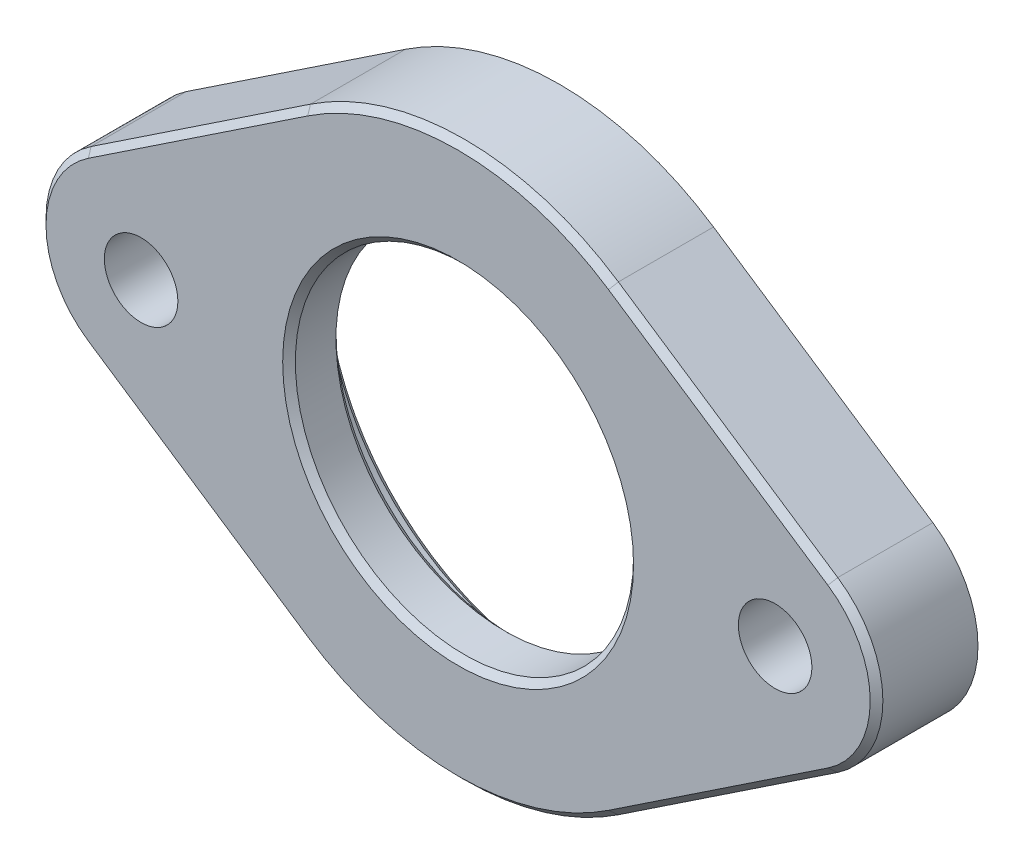
SolidWorks part; units mm, degrees
material "ABS"
ref_plane "Front Plane" through (0, 0, 0) normal (0, 0, 1) x (1, 0, 0)
ref_plane "Top Plane" through (0, 0, 0) normal (0, 1, 0) x (1, 0, 0)
ref_plane "Right Plane" through (0, 0, 0) normal (1, 0, 0) x (0, 0, -1)
sketch "Sketch1" plane through (0, 0, 0) normal (0, 0, 1) x (1, 0, 0)
  line L0 (-12.5, 0) -> (12.5, 0)
  line L1 (-6.0703, -9.0984) -> (-14.72, -3.3274)
  line L2 (-6.0703, 9.0984) -> (-14.72, 3.3274)
  line L3 (6.0703, 9.0984) -> (14.72, 3.3274)
  line L4 (6.0703, -9.0984) -> (14.72, -3.3274)
  circle A0 centre (0, 0) radius 6.6675
  circle A1 centre (0, 0) radius 8.9375
  circle A2 centre (0, 0) radius 10.9375
  circle A3 centre (-12.5, 0) radius 4
  circle A4 centre (12.5, 0) radius 4
  point P7 (0, 0)
  dimension "D1" = 13.335
  dimension "D2" = 17.875
  dimension "D4" = 8
  dimension "D3" = 2
  dimension "D5" = 25
extrude "Boss-Extrude1" add sketch "Sketch1" along normal blind 4 contours A3 L0 A2 L2 | A3 L1 A2 L0 | A3 | A4 L3 A2 L0 | A4 | A4 L0 A2 L4 | A2 region at (13.2988, 0, 0) region at (10.617, 5.2562, 0) region at (10.617, -5.2562, 0) region at (-10.617, 5.2562, 0) region at (-13.2988, 0, 0) region at (-10.617, -5.2562, 0)
extrude "Cut-Extrude1" cut sketch "Sketch1<4>" against normal through all both and the other way through all contours L0 A0 | L0 A0 region at (0, -2.8298, 0) region at (0, 2.8298, 0)
sketch "Sketch1<4>" plane through (0, 0, 0) normal (0, 0, 1) x (1, 0, 0) same geometry as "Sketch1"
extrude "Cut-Extrude2" cut sketch "Sketch1<6>" along normal blind 1.9 and the other way through all contours A1
sketch "Sketch1<6>" plane through (0, 0, 0) normal (0, 0, 1) x (1, 0, 0) same geometry as "Sketch1"
sketch "Sketch2" plane through (0, 0, 4) normal (0, 0, 1) x (1, 0, 0)
  point P0 (-12.5, 0)
  point P3 (12.5, 0)
hole_wizard "M2.5 Clearance Hole1" positions "Sketch2" profile "Sketch3" hole size "M2.5" standard "ANSI Metric" end condition through all
sketch "Sketch3" plane through (-12.5, 0, 4) normal (1, 0, 0) x (0, -1, 0)
  line L0 (0, 0) -> (0, 4)
  line L1 (0, 4) -> (1.45, 4)
  line L2 (1.45, 4) -> (1.45, 0)
  line L5 (1.45, 0) -> (0, 0)
  line L11 (0, -6.35) -> (0, 107.95) construction
  dimension "Thru Hole Dia." = 2.9
  dimension "Thru Hole Depth" = 4
chamfer "Chamfer1" distance 0.25 angle 45 12 edges at (6.6675, 0, 4) (6.6675, 0, 1.9) (8.9375, 0, 0) (8.9375, 0, 1.9) (10.3952, -6.2129, 4) (16.5, 0, 4) (0, -10.9375, 4) (10.3952, 6.2129, 4) (-10.3952, -6.2129, 4) (0, 10.9375, 4) (-16.5, 0, 4) (-10.3952, 6.2129, 4)
equation "\"D2@Sketch1\"=15.875mm+2"
